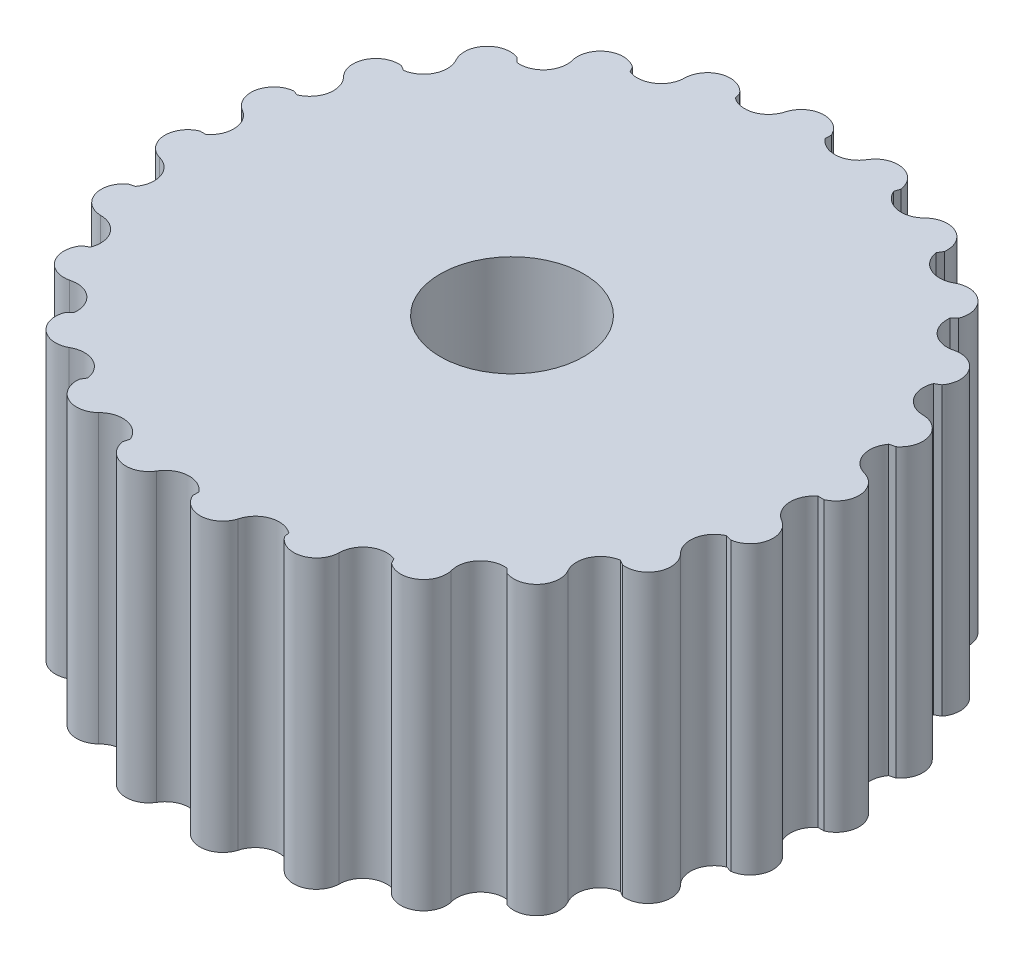
SolidWorks part; units mm, degrees
note: '?' marks a value the reader was unsure of.
ref_plane "Front Plane" through (0, 0, 0) normal (0, 0, 1) x (1, 0, 0)
ref_plane "Top Plane" through (0, 0, 0) normal (0, 1, 0) x (1, 0, 0)
ref_plane "Right Plane" through (0, 0, 0) normal (1, 0, 0) x (0, 0, -1)
sketch "Sketch1" plane through (0, 0, 0) normal (0, 1, 0) x (1, 0, 0)
  line L0 (0, 5.25) -> (0, 5.75) construction
  line L1 (0.7149, 5.2011) -> (0.783, 5.6964) construction
  line L2 (1.4164, 5.0553) -> (1.5513, 5.5368) construction
  line L3 (0, 5.5) -> (0, 1.25)
  line L4 (0.3372, 1.2036) -> (1.4839, 5.296)
  circle A0 centre (0, 0) radius 5.25 construction
  arc A1 (0, 5.5) -> (0.7489, 5.4488) centre (0.3866, 5.6524) ccw
  arc A2 (1.5513, 5.5368) -> (0, 5.75) centre (0, 0) ccw construction
  arc A3 (0.7489, 5.4488) -> (1.4839, 5.296) centre (1.0886, 5.2387) cw
  arc A4 (0.3372, 1.2036) -> (0, 1.25) centre (0, 0) ccw
  point P6 (0, 5.5)
  point P9 (0.7489, 5.4488)
  dimension "D1" = 10.5
  dimension "D2" = 0.5
  dimension "D3" = 2.5
extrude "Boss-Extrude1" add sketch "Sketch1" along normal blind 5
pattern_circular "CirPattern1" count 24 over 360 about axis through (0, 0, 0) along (0, 1, 0) of "Boss-Extrude1"
ref_axis "Axis1" through (0, 0, 0) along (0, 1, 0)?
sketch "Sketch2" plane through (0, 5, 0) normal (0, 1, 0) x (1, 0, 0)
  line L0 (0, 74.1691) -> (0, -78.0459) construction
  line L1 (4.7625, 3.175) -> (6.6675, 3.175)
  line L2 (4.7625, 3.175) -> (4.7625, -3.175)
  line L3 (4.7625, -3.175) -> (6.6675, -3.175)
  line L4 (6.6675, 3.175) -> (6.6675, -3.175)
  line L5 (-6.6675, 3.175) -> (-6.6675, -3.175)
  line L6 (-4.7625, -3.175) -> (-6.6675, -3.175)
  line L7 (-4.7625, 3.175) -> (-4.7625, -3.175)
  line L8 (-4.7625, 3.175) -> (-6.6675, 3.175)
  point P6 (4.7625, 0)
  point P12 (-4.7625, 0)
  dimension "D1" = 1.905
  dimension "D2" = 6.35
  dimension "D3" = 4.7625
